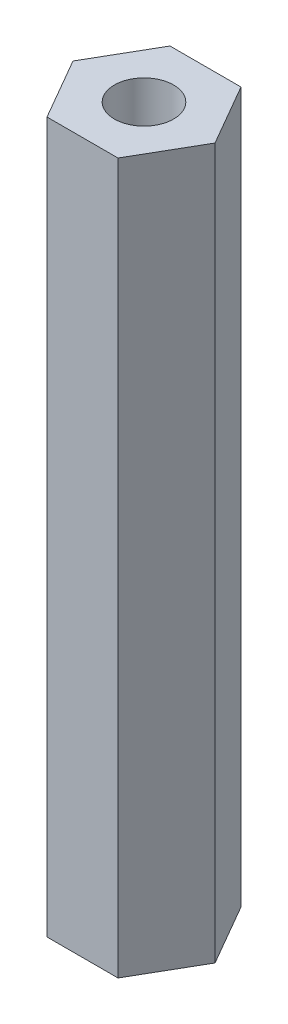
SolidWorks part; units mm, degrees
ref_plane "前视基准面" through (0, 0, 0) normal (0, 0, 1) x (1, 0, 0)
ref_plane "上视基准面" through (0, 0, 0) normal (0, 1, 0) x (1, 0, 0)
ref_plane "右视基准面" through (0, 0, 0) normal (1, 0, 0) x (0, 0, -1)
sketch "草图1" plane through (0, 0, 0) normal (0, 1, 0) x (1, 0, 0)
  line L1 (1.5, 2.5981) -> (-1.5, 2.5981)
  line L2 (-1.5, 2.5981) -> (-3, 0)
  line L3 (-3, 0) -> (-1.5, -2.5981)
  line L4 (-1.5, -2.5981) -> (1.5, -2.5981)
  line L5 (1.5, -2.5981) -> (3, 0)
  line L6 (3, 0) -> (1.5, 2.5981)
  circle A0 centre (0, 0) radius 2.5981 construction
  dimension "D1" = 3
extrude "凸台-拉伸1" add sketch "草图1" along normal blind 30
hole_wizard "M3 螺纹孔1" positions "草图2" profile "草图3" tap size "M3" standard "GB" end condition through all
sketch "草图2" plane through (0, 30, 0) normal (0, 1, 0) x (1, 0, 0)
  point P0 (0, 0)
sketch "草图3" plane through (0, 30, 0) normal (1, 0, 0) x (0, 0, 1)
  line L0 (0, 0) -> (0, 30)
  line L1 (0, 30) -> (1.25, 30)
  line L2 (1.25, 30) -> (1.25, 0)
  line L5 (1.25, 0) -> (0, 0)
  line L11 (0, -6.35) -> (0, 107.95) construction
  dimension "通孔螺纹孔钻头直径" = 2.5
  dimension "通孔螺纹孔钻头深度" = 30
cosmetic thread "孔螺蚊线1" parameters "D2"=3
